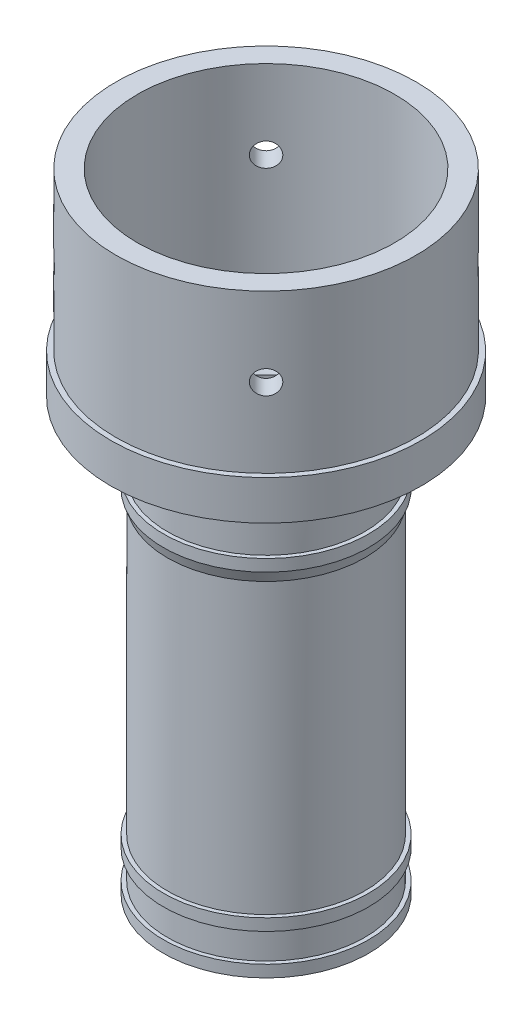
SolidWorks part; units mm, degrees
ref_plane "Front Plane" through (0, 0, 0) normal (0, 0, 1) x (1, 0, 0)
ref_plane "Top Plane" through (0, 0, 0) normal (0, 1, 0) x (1, 0, 0)
ref_plane "Right Plane" through (0, 0, 0) normal (1, 0, 0) x (0, 0, -1)
sketch "Sketch2" plane through (0, 0, 0) normal (0, 1, 0) x (1, 0, 0)
  circle A0 centre (0, 0) radius 20.85
  circle A1 centre (0, 0) radius 25
  dimension "D1" = 41.7
  dimension "D2" = 50
extrude "Boss-Extrude1" add sketch "Sketch2" along normal blind 99.25
sketch "Sketch3" plane through (0, 99.25, 0) normal (0, 1, 0) x (1, 0, 0)
  circle A0 centre (0, 0) radius 38.05
  circle A1 centre (0, 0) radius 32.6
  dimension "D1" = 76.1
  dimension "D2" = 65.2
extrude "Boss-Extrude2" add sketch "Sketch3" along normal blind 50 from offset 10 separate body
loft "Loft3" add section edge at (0, 99.25, 25) section edge at (0, 109.25, 38.05) connector at (-24.9573, 99.25, -1.46) connector at (-37.8357, 109.25, -4.0328)
loft "Cut-Loft1" cut section edge at (0, 99.25, 20.85) section edge at (0, 109.25, 32.6) connector at (-19.8577, 99.25, 6.3557) connector at (-21.2963, 109.25, 24.6825)
sketch "Sketch4" plane through (0, 159.25, 0) normal (0, 1, 0) x (1, 0, 0)
  circle A0 centre (0, 0) radius 38.05
  circle A1 centre (0, 0) radius 39.35
  dimension "D1" = 78.7
  dimension "D2" = 76.1
extrude "Boss-Extrude3" add sketch "Sketch4" along normal blind 10 from offset 50 offset against normal yes
ref_plane "Plane1" through (-26.9054, 0, 26.9054) normal (-0.7071, 0, 0.7071) x (0, -1, 0)
sketch "Sketch7" plane through (-26.9054, 0, 26.9054) normal (-0.7071, 0, 0.7071) x (0, -1, 0)
  line L0 (-159.25, 38.05) -> (-159.25, -38.05) construction
  circle A0 centre (-139.25, 0) radius 3
  dimension "D1" = 20
extrude "Cut-Extrude1" cut sketch "Sketch7" against normal up to next
pattern_circular "CirPattern1" count 4 over 360 about axis through (0, 159.25, 0) along (0, -1, 0) of "Cut-Extrude1" reverse direction yes
sketch "Sketch8" plane through (0, 0, 0) normal (0, -1, 0) x (1, 0, 0)
  circle A0 centre (0, 0) radius 26
  circle A1 centre (0, 0) radius 25
extrude "Boss-Extrude5" add sketch "Sketch8" against normal blind 3
sketch "Sketch9" plane through (0, 0, 0) normal (0, -1, 0) x (1, 0, 0)
  circle A0 centre (0, 0) radius 26
  circle A1 centre (0, 0) radius 25
extrude "Boss-Extrude6" add sketch "Sketch9" along normal blind 6 from offset 92.05 offset against normal yes
chamfer "Chamfer1" distance 3 angle 20 1 edges at (0, 86.05, -26) first distance on face at (0, 86.05, -26)
sketch "Sketch10" plane through (0, 0, 0) normal (0, -1, 0) x (1, 0, 0)
  circle A0 centre (0, 0) radius 26
  circle A1 centre (0, 0) radius 25
  dimension "D1" = 50
  dimension "D2" = 52
extrude "Boss-Extrude7" add sketch "Sketch10" against normal blind 3 from offset 10.2 offset against normal yes
